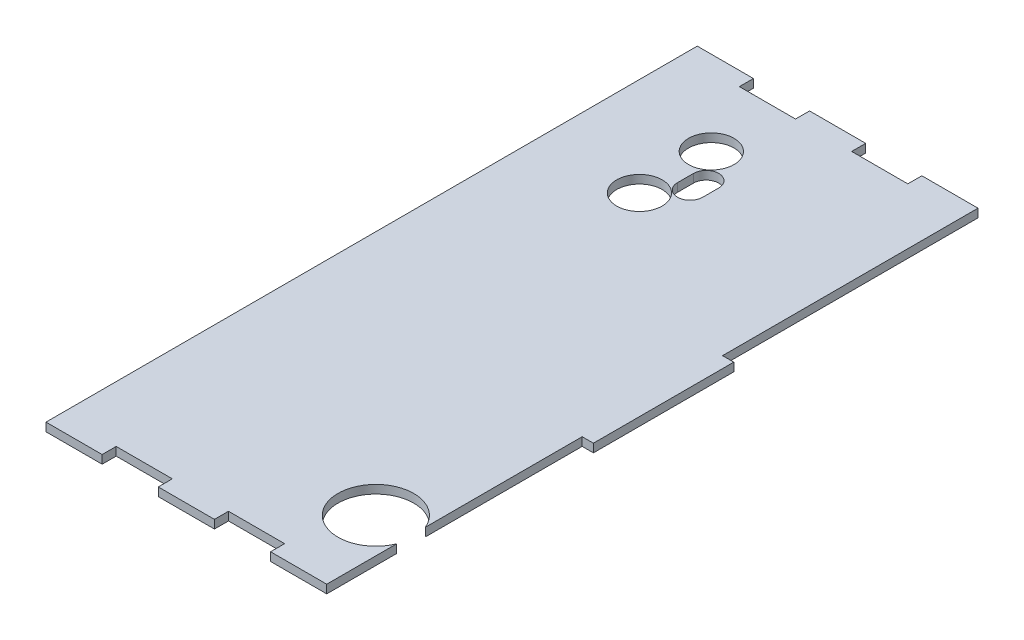
SolidWorks part; units mm, degrees
ref_plane "Front Plane" through (0, 0, 0) normal (0, 0, 1) x (1, 0, 0)
ref_plane "Top Plane" through (0, 0, 0) normal (0, 1, 0) x (1, 0, 0)
ref_plane "Right Plane" through (0, 0, 0) normal (1, 0, 0) x (0, 0, -1)
sketch "Sketch1" plane through (0, 0, 0) normal (0, 1, 0) x (1, 0, 0)
  line L0 (-50, -111) -> (-50, -116)
  line L1 (30, 111) -> (10, 111)
  line L2 (50, 111) -> (50, 25)
  line L3 (30, -111) -> (10, -111)
  line L4 (-50, 111) -> (-50, -111)
  line L5 (50, 111) -> (-50, -111) construction
  line L6 (50, -111) -> (-50, 111) construction
  line L7 (-50, -116) -> (-30, -116)
  line L8 (-30, -116) -> (-30, -111)
  line L9 (-10, -111) -> (-10, -116)
  line L10 (-10, -116) -> (10, -116)
  line L11 (10, -116) -> (10, -111)
  line L12 (30, -111) -> (30, -116)
  line L13 (30, -116) -> (50, -116)
  line L14 (50, -116) -> (50, -111)
  line L15 (-50, 0) -> (50, 0) construction
  line L16 (0, -116) -> (0, 116) construction
  line L17 (50, 116) -> (50, 111)
  line L18 (30, 116) -> (50, 116)
  line L19 (30, 111) -> (30, 116)
  line L20 (10, 116) -> (10, 111)
  line L21 (-10, 116) -> (10, 116)
  line L22 (-10, 111) -> (-10, 116)
  line L23 (-30, 116) -> (-30, 111)
  line L24 (-50, 116) -> (-30, 116)
  line L25 (-50, 111) -> (-50, 116)
  line L26 (-10, 111) -> (-30, 111)
  line L27 (-10, -111) -> (-30, -111)
  line L28 (50, -25) -> (50, -80.901)
  line L29 (50, -25) -> (54, -25)
  line L31 (50, 25) -> (54, 25)
  line L32 (54, -25) -> (54, 25)
  line L35 (-15, 60.4) -> (-15, 86) construction
  line L36 (50, -91.099) -> (50, -111)
  line L37 (-11.4, 70.35) -> (-11.4, 76.05)
  line L38 (-2.4, 70.35) -> (-2.4, 76.05)
  circle A4 centre (-15, 60.4) radius 8.1
  circle A5 centre (-15, 86) radius 8.1
  arc A6 (-11.4, 70.35) -> (-2.4, 70.35) centre (-6.9, 70.35) ccw
  arc A7 (-2.4, 76.05) -> (-11.4, 76.05) centre (-6.9, 76.05) ccw
  arc A8 (50, -80.901) -> (50, -91.099) centre (37.5, -86) ccw
  point P0 (0, 0)
  dimension "D8" = 16.2
  dimension "D9" = 16.2
  dimension "D14" = 9
  dimension "D15" = 9
  dimension "D21" = 27
  dimension "D1" = 100
  dimension "D2" = 222
  dimension "D3" = 5
  dimension "D4" = 20
  dimension "D6" = 50
  dimension "D7" = 4
  dimension "D10" = 25.6
  dimension "D11" = 8.1
  dimension "D12" = 8.1
  dimension "D13" = 5.7
  dimension "D16" = 25
  dimension "D17" = 9.95
  dimension "D18" = 65
  dimension "D19" = 5.7
  dimension "D20" = 5.7
  dimension "D22" = 12.5
  dimension "D23" = 25
  dimension "D24" = 86
  dimension "D5" = 3
extrude "Boss-Extrude1" add sketch "Sketch1" along normal blind 3
